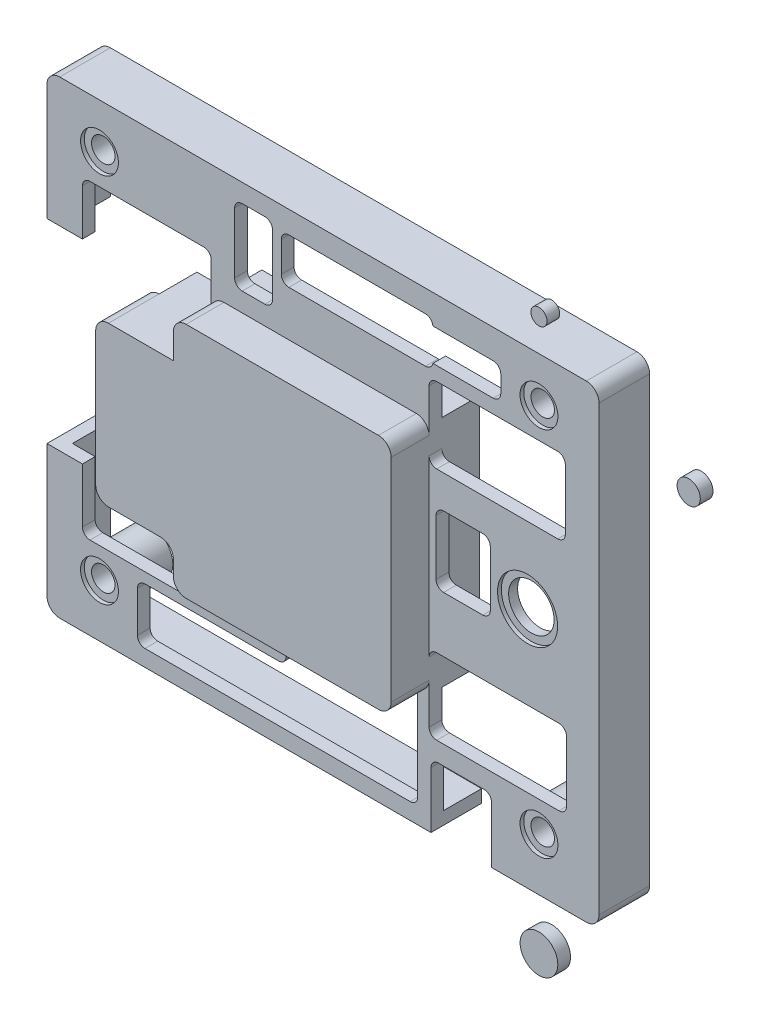
SolidWorks part; units mm, degrees
ref_plane "前视基准面" through (0, 0, 0) normal (0, 0, 1) x (1, 0, 0)
ref_plane "上视基准面" through (0, 0, 0) normal (0, 1, 0) x (1, 0, 0)
ref_plane "右视基准面" through (0, 0, 0) normal (1, 0, 0) x (0, 0, -1)
sketch "草图1" plane through (0, 0, 0) normal (0, 0, 1) x (1, 0, 0)
  line L1 (-76.2588, 51.6727) -> (-18.2588, 51.6727) construction
  line L2 (-76.2588, 51.6727) -> (-76.2588, 2.6727) construction
  line L3 (-76.2588, 2.6727) -> (-18.2588, 2.6727) construction
  line L4 (-18.2588, 51.6727) -> (-18.2588, 2.6727) construction
  line L5 (-76.2588, 51.6727) -> (-18.2588, 2.6727) construction
  line L6 (-76.2588, 2.6727) -> (-18.2588, 51.6727) construction
  line L7 (-80.5088, 55.9227) -> (-14.0088, 55.9227) construction
  line L8 (-80.5088, 55.9227) -> (-80.5088, -1.5773) construction
  line L9 (-80.5088, -1.5773) -> (-14.0088, -1.5773) construction
  line L10 (-14.0088, 55.9227) -> (-14.0088, -1.5773) construction
  line L11 (-80.5088, 55.9227) -> (-14.0088, -1.5773) construction
  line L12 (-80.5088, -1.5773) -> (-14.0088, 55.9227) construction
  line L13 (-83.1888, 57.6027) -> (-10.3288, 57.6027)
  line L14 (-83.1888, 57.6027) -> (-83.1888, -4.2573)
  line L15 (-83.1888, -4.2573) -> (-10.3288, -4.2573)
  line L16 (-10.3288, 57.6027) -> (-10.3288, -4.2573)
  circle A0 centre (-76.2588, 51.6727) radius 1.55
  circle A1 centre (-18.2588, 51.6727) radius 1.55
  circle A2 centre (-76.2588, 2.6727) radius 1.55
  circle A3 centre (-18.2588, 2.6727) radius 1.55
  circle A4 centre (1.5043, 51.6727) radius 1.5315
  circle A5 centre (-18.2588, 61.841) radius 1.0639
  circle A6 centre (-18.2588, -10.9758) radius 2.4893
  point P0 (-47.2588, 27.1727)
  point P9 (-47.2588, 27.1727)
  point P14 (-47.2588, 27.1727)
  dimension "D3" = 57.5
  dimension "D1" = 49
  dimension "D2" = 58
  dimension "D4" = 66.5
  dimension "D5" = 2.68
  dimension "D6" = 3.68
  dimension "D7" = 1.68
  dimension "D8" = 2.68
extrude "凸台-拉伸1" add sketch "草图1" along normal blind 1.68
sketch "草图2" plane through (0, 0, 1.68) normal (0, 0, 1) x (1, 0, 0)
  circle A0 centre (-76.2588, 2.6727) radius 3
  circle A1 centre (-18.2588, 2.6727) radius 3
  circle A2 centre (-76.2588, 51.6727) radius 3
  circle A3 centre (-18.2588, 51.6727) radius 3
  circle A4 centre (-76.2588, 51.6727) radius 1.55
  circle A5 centre (-18.2588, 51.6727) radius 1.55
  circle A6 centre (-76.2588, 2.6727) radius 1.55
  circle A7 centre (-18.2588, 2.6727) radius 1.55
  dimension "D1" = 6
  dimension "D2" = 6
extrude "凸台-拉伸3" add sketch "草图2" against normal blind 6.68
sketch "草图3" plane through (0, 0, 1.68) normal (0, 0, 1) x (1, 0, 0)
  line L1 (-83.1888, 57.6027) -> (-10.3288, 57.6027)
  line L2 (-83.1888, 57.6027) -> (-83.1888, -4.2573)
  line L3 (-83.1888, -4.2573) -> (-10.3288, -4.2573)
  line L4 (-10.3288, 57.6027) -> (-10.3288, -4.2573)
  line L5 (-12.0075, -2.5773) -> (-81.5088, -2.5773)
  line L6 (-12.0075, -2.5773) -> (-12.0075, 55.9227)
  line L7 (-12.0075, 55.9227) -> (-81.5088, 55.9227)
  line L8 (-81.5088, -2.5773) -> (-81.5088, 55.9227)
  dimension "D1" = 1.68
  dimension "D2" = 1.68
  dimension "D3" = 1.68
  dimension "D4" = 1.6787
extrude "凸台-拉伸4" add sketch "草图3" against normal blind 6.68
sketch "草图4" plane through (0, 0, 1.68) normal (0, 0, 1) x (1, 0, 0)
  line L0 (-83.1888, 57.6027) -> (-83.1888, -4.2573) construction
  line L2 (-83.1888, 40.5767) -> (-83.1888, 14.8691)
  line L3 (-83.1888, 14.8691) -> (-71.7588, 14.8691) construction
  line L4 (-31.8362, 33.329) -> (-24.6813, 33.329)
  line L5 (-31.8362, 33.329) -> (-31.8362, 24.0163)
  line L6 (-76.2588, 2.6727) -> (-80.9225, 2.6727) construction
  line L7 (-76.2588, 2.6727) -> (-76.2588, 6.406) construction
  line L8 (-18.2588, 51.6727) -> (-18.2588, 47.2167) construction
  line L9 (-83.1888, -4.2573) -> (-10.3288, -4.2573) construction
  line L10 (-31.8362, 24.0163) -> (-24.6813, 24.0163)
  line L11 (-78.5088, 16.6727) -> (-78.5088, 6.6727) construction
  line L12 (-78.5088, 6.6727) -> (-61.5088, 6.6727)
  line L13 (-61.5088, 16.6727) -> (-61.5088, 6.6727)
  line L14 (-76.2588, 47.6727) -> (-61.5088, 47.6727)
  line L15 (-24.6813, 33.329) -> (-24.6813, 24.0163)
  line L16 (-31.8362, 33.329) -> (-24.6813, 24.0163) construction
  line L17 (-61.5088, 47.6727) -> (-61.5088, 37.6727)
  line L18 (-58.4245, 55.1727) -> (-53.4245, 55.1727)
  line L19 (-58.4245, 55.1727) -> (-58.4245, 45.1727)
  line L20 (-58.4245, 45.1727) -> (-53.4245, 45.1727)
  line L21 (-53.4245, 55.1727) -> (-53.4245, 45.1727)
  line L22 (-52.2588, 54.6727) -> (-32.2588, 54.6727)
  line L23 (-52.2588, 54.6727) -> (-52.2588, 48.6775)
  line L24 (-52.2588, 48.6775) -> (-32.2588, 48.6775)
  line L25 (-32.2588, 54.6727) -> (-32.2588, 48.6775) construction
  line L26 (-31.2588, 31.6727) -> (-25.2588, 31.6727) construction
  line L27 (-31.2588, 31.6727) -> (-31.2588, 25.6727) construction
  line L28 (-31.2588, 25.6727) -> (-25.2588, 25.6727) construction
  line L29 (-25.2588, 31.6727) -> (-25.2588, 25.6727) construction
  line L30 (-32.7588, 47.6727) -> (-14.7786, 47.6727)
  line L31 (-32.7588, 47.6727) -> (-32.7588, 37.6727)
  line L32 (-32.7588, 37.6727) -> (-14.7786, 37.6727)
  line L33 (-14.7786, 47.6727) -> (-14.7786, 37.6727)
  line L34 (-32.7588, 16.6727) -> (-14.6177, 16.6727)
  line L35 (-32.7588, 16.6727) -> (-32.7588, 6.6727)
  line L36 (-32.7588, 6.6727) -> (-14.6177, 6.6727)
  line L37 (-14.6177, 16.6727) -> (-14.6177, 6.6727)
  line L38 (-71.2588, -2.0909) -> (-34.2588, -2.0909)
  line L39 (-71.2588, -2.0909) -> (-71.2588, 11.3699) construction
  line L40 (-71.2588, 11.3699) -> (-34.2588, 11.3699) construction
  line L41 (-34.2588, -2.0909) -> (-34.2588, 11.3699)
  line L42 (-32.5088, 4.1759) -> (-24.5088, 4.1759)
  line L43 (-32.5088, 4.1759) -> (-32.5088, -4.2573)
  line L44 (-32.5088, -4.2573) -> (-24.5088, -4.2573)
  line L45 (-24.5088, 4.1759) -> (-24.5088, -4.2573)
  line L46 (-78.5088, 11.6727) -> (-72.716, 11.6727) construction
  line L47 (-18.2588, 51.6727) -> (-14.191, 51.6727) construction
  line L48 (-31.8362, 24.0163) -> (-24.6813, 33.329) construction
  line L51 (-76.2588, 47.6727) -> (-78.5088, 47.6727)
  line L52 (-78.5088, 47.6727) -> (-78.5088, 40.5767)
  line L53 (-61.5088, 37.6727) -> (-71.7588, 37.6727)
  line L54 (-71.7588, 37.6727) -> (-71.7588, 16.6727)
  line L55 (-71.7588, 16.6727) -> (-61.5088, 16.6727)
  line L56 (-83.1888, 14.8691) -> (-78.5088, 14.8691)
  line L57 (-78.5088, 14.8691) -> (-78.5088, 6.6727)
  line L58 (-32.2588, 49.491) -> (-32.2588, 48.6775)
  line L59 (-32.2588, 53.7648) -> (-23.2977, 53.7648)
  line L60 (-32.2588, 53.7648) -> (-32.2588, 49.491) construction
  line L61 (-32.2588, 49.491) -> (-23.2977, 49.491)
  line L62 (-23.2977, 53.7648) -> (-23.2977, 49.491)
  line L63 (-32.2588, 53.7648) -> (-32.2588, 54.6727)
  line L64 (-71.2588, -2.0909) -> (-71.2588, 5.2905)
  line L65 (-71.2588, 5.2905) -> (-51.6311, 5.2905)
  line L66 (-51.6311, 5.2905) -> (-51.6311, 11.3699)
  line L67 (-51.6311, 11.3699) -> (-34.2588, 11.3699)
  line L68 (-78.5088, 40.5767) -> (-83.1888, 40.5767)
  circle A0 centre (-19.7588, 27.6727) radius 3
  point P3 (-28.2588, 28.6727)
  point P68 (-24.5088, -0.0407)
  dimension "D32" = 6
  dimension "D5" = 10
  dimension "D6" = 10
  dimension "D8" = 17
  dimension "D9" = 17
  dimension "D12" = 9
  dimension "D13" = 2.25
  dimension "D16" = 5
  dimension "D17" = 10
  dimension "D19" = 3.5
  dimension "D20" = 5.9951
  dimension "D21" = 20
  dimension "D22" = 3
  dimension "D23" = 24
  dimension "D26" = 0
  dimension "D31" = 1.5
  dimension "D33" = 25
  dimension "D34" = 37
  dimension "D36" = 5
  dimension "D37" = 8
  dimension "D38" = 6.25
extrude "切除-拉伸1" cut sketch "草图4" against normal blind 10
sketch "草图5" plane through (0, 0, 1.68) normal (0, 0, 1) x (1, 0, 0)
  line L0 (-71.7588, 37.6727) -> (-71.7588, 16.6727)
  line L1 (-71.7588, 37.6727) -> (-32.7588, 37.6727) construction
  line L2 (-71.7588, 37.6727) -> (-71.7588, 16.6727) construction
  line L3 (-71.7588, 16.6727) -> (-32.7588, 16.6727) construction
  line L4 (-32.7588, 37.6727) -> (-32.7588, 16.6727) construction
  line L5 (-71.7588, 16.6727) -> (-61.5088, 16.6727)
  line L6 (-61.5088, 6.6727) -> (-61.5088, 16.6727) construction
  line L7 (-61.5088, 16.6727) -> (-61.5088, 11.3486)
  line L8 (-61.5088, 11.3486) -> (-32.7588, 11.3486)
  line L9 (-32.7588, 16.6727) -> (-32.7588, 6.6727) construction
  line L10 (-32.7588, 11.3486) -> (-32.7588, 42.6727)
  line L11 (-32.7588, 47.6727) -> (-32.7588, 37.6727) construction
  line L12 (-32.7588, 42.6727) -> (-61.5088, 42.6727)
  line L13 (-61.5088, 37.6727) -> (-61.5088, 47.6727) construction
  line L14 (-61.5088, 42.6727) -> (-61.5088, 37.6727)
  line L15 (-61.5088, 37.6727) -> (-71.7588, 37.6727)
extrude "凸台-拉伸5" add sketch "草图5" along normal blind 5
sketch "草图6" plane through (0, 0, 0) normal (0, 0, -1) x (-1, 0, 0)
  line L0 (61.5088, 16.6727) -> (71.7588, 16.6727) construction
  line L1 (70.0788, 35.9927) -> (34.4388, 35.9927) construction
  line L2 (70.0788, 35.9927) -> (70.0788, 18.3527) construction
  line L3 (70.0788, 18.3527) -> (34.4388, 18.3527) construction
  line L4 (34.4388, 35.9927) -> (34.4388, 18.3527) construction
  line L5 (71.7588, 16.6727) -> (71.7588, 37.6727) construction
  line L6 (71.7588, 37.6727) -> (61.5088, 37.6727) construction
  line L7 (32.7588, 47.6727) -> (32.7588, 37.6727) construction
  line L8 (34.4388, 35.9927) -> (34.4388, 18.3527)
  line L9 (34.4388, 18.3527) -> (34.4388, 14.075)
  line L10 (34.4388, 14.075) -> (60.0851, 14.075)
  line L11 (60.0851, 14.075) -> (60.0851, 18.3527)
  line L12 (60.0851, 18.3527) -> (70.0788, 18.3527)
  line L13 (70.0788, 18.3527) -> (70.0788, 35.9927)
  line L14 (70.0788, 35.9927) -> (60.0851, 35.9927)
  line L15 (60.0851, 35.9927) -> (60.0851, 39.9984)
  line L16 (60.0851, 39.9984) -> (34.4388, 39.9984)
  line L17 (34.4388, 39.9984) -> (34.4388, 35.9927)
  point P10 (66.6338, 37.6727)
  dimension "D1" = 1.68
  dimension "D2" = 1.68
  dimension "D3" = 1.68
  dimension "D4" = 1.68
extrude "切除-拉伸2" cut sketch "草图6" against normal blind 5
fillet "圆角1" radius 1.68 8 edges at (-12.0075, 55.9227, -2.5) (-81.5088, 55.9227, -2.5) (-81.5088, -2.5773, -2.5) (-83.1888, -4.2573, -1.66) (-12.0075, -2.5773, -2.5) (-10.3288, -4.2573, -1.66) (-10.3288, 57.6027, -1.66) (-83.1888, 57.6027, -1.66)
fillet "圆角2" radius 1.68 7 edges at (-61.5088, 11.3486, 4.18) (-61.5088, 16.6727, 3.34) (-71.7588, 16.6727, 3.34) (-71.7588, 37.6727, 3.34) (-61.5088, 42.6727, 4.18) (-32.7588, 11.3486, 4.18) (-32.7588, 42.6727, 4.18)
fillet "圆角3" radius 1 32 edges at (-23.2977, 53.7648, 0.84) (-23.2977, 49.491, 0.84) (-32.2588, 48.6775, 0.84) (-32.2588, 54.6727, 0.84) (-52.2588, 48.6775, 0.84) (-52.2588, 54.6727, 0.84) (-58.4245, 55.1727, 0.84) (-53.4245, 55.1727, 0.84) (-53.4245, 45.1727, 0.84) (-58.4245, 45.1727, 0.84) (-78.5088, 47.6727, 0.84) (-61.5088, 47.6727, 0.84) (-61.5088, 6.6727, 0.84) (-78.5088, 6.6727, 0.84) (-71.2588, -2.0909, 0.84) (-71.2588, 5.2905, 0.84) (-51.6311, 5.2905, 0.84) (-34.2588, -2.0909, 0.84) (-32.5088, 4.1759, 0.84) (-24.5088, 4.1759, 0.84) (-32.7588, 16.6727, 0.84) (-14.6177, 16.6727, 0.84) (-14.6177, 6.6727, 0.84) (-32.7588, 6.6727, 0.84) (-32.7588, 37.6727, 0.84) (-32.7588, 47.6727, 0.84) (-14.7786, 47.6727, 0.84) (-14.7786, 37.6727, 0.84) (-24.6813, 24.0163, 0.84) (-24.6813, 33.329, 0.84) (-31.8362, 33.329, 0.84) (-31.8362, 24.0163, 0.84)
sketch "草图7" plane through (0, 0, 1.68) normal (0, 0, 1) x (1, 0, 0)
  circle A0 centre (-76.2588, 51.6727) radius 2.5
  circle A1 centre (-76.2588, 2.6727) radius 2.5
  circle A2 centre (-18.2588, 2.6727) radius 2.5
  circle A3 centre (-18.2588, 51.6727) radius 2.5
  circle A4 centre (-19.7588, 27.6727) radius 3.9643
extrude "切除-拉伸3" cut sketch "草图7" against normal blind 0.5
sketch "草图8" plane through (0, 0, 0) normal (0, 0, -1) x (-1, 0, 0)
  line L0 (51.6311, 11.3699) -> (32.7588, 11.3699)
  line L1 (32.7588, 15.6727) -> (32.7588, 7.6727) construction
  line L2 (32.7588, 11.3699) -> (32.7588, 42.2051)
  line L3 (32.7588, 46.6727) -> (32.7588, 38.6727) construction
  line L4 (32.7588, 42.2051) -> (61.5088, 42.2051)
  line L5 (61.5088, 37.6727) -> (61.5088, 46.6727) construction
  line L6 (61.5088, 42.2051) -> (61.5088, 37.6727)
  line L7 (61.5088, 37.6727) -> (70.0788, 37.6727)
  line L8 (70.0788, 37.6727) -> (71.7588, 35.9927)
  line L9 (71.7588, 35.9927) -> (71.7588, 18.3527)
  line L10 (71.7588, 18.3527) -> (70.0788, 16.6727)
  line L11 (70.0788, 16.6727) -> (63.1888, 16.6727)
  line L12 (63.1888, 16.6727) -> (61.5088, 16.6727)
  line L13 (61.5088, 16.6727) -> (61.5088, 11.6727)
  line L14 (61.5088, 7.6727) -> (61.5088, 14.9927) construction
  line L15 (61.5088, 11.6727) -> (61.5088, 11.3699)
  line L16 (61.5088, 11.3699) -> (51.6311, 11.3699)
  line L17 (60.0851, 14.075) -> (60.0851, 18.3527)
  line L18 (60.0851, 18.3527) -> (70.0788, 18.3527)
  line L19 (70.0788, 18.3527) -> (70.0788, 35.9927)
  line L20 (70.0788, 35.9927) -> (60.0851, 35.9927)
  line L21 (60.0851, 35.9927) -> (60.0851, 39.9984)
  line L22 (60.0851, 39.9984) -> (34.4388, 39.9984)
  line L23 (34.4388, 39.9984) -> (34.4388, 14.075)
  line L24 (34.4388, 39.9984) -> (34.4388, 14.075) construction
  line L25 (34.4388, 14.075) -> (60.0851, 14.075) construction
  line L26 (34.4388, 14.075) -> (60.0851, 14.075)
  arc A0 (71.7588, 35.9927) -> (70.0788, 37.6727) centre (70.0788, 35.9927) ccw construction
  arc A1 (70.0788, 16.6727) -> (71.7588, 18.3527) centre (70.0788, 18.3527) ccw construction
extrude "凸台-拉伸6" add sketch "草图8" along normal up to surface (5 mm away) up to face at (-39.695, 32.0054, -5)
equation "\"0。5\"=10"
